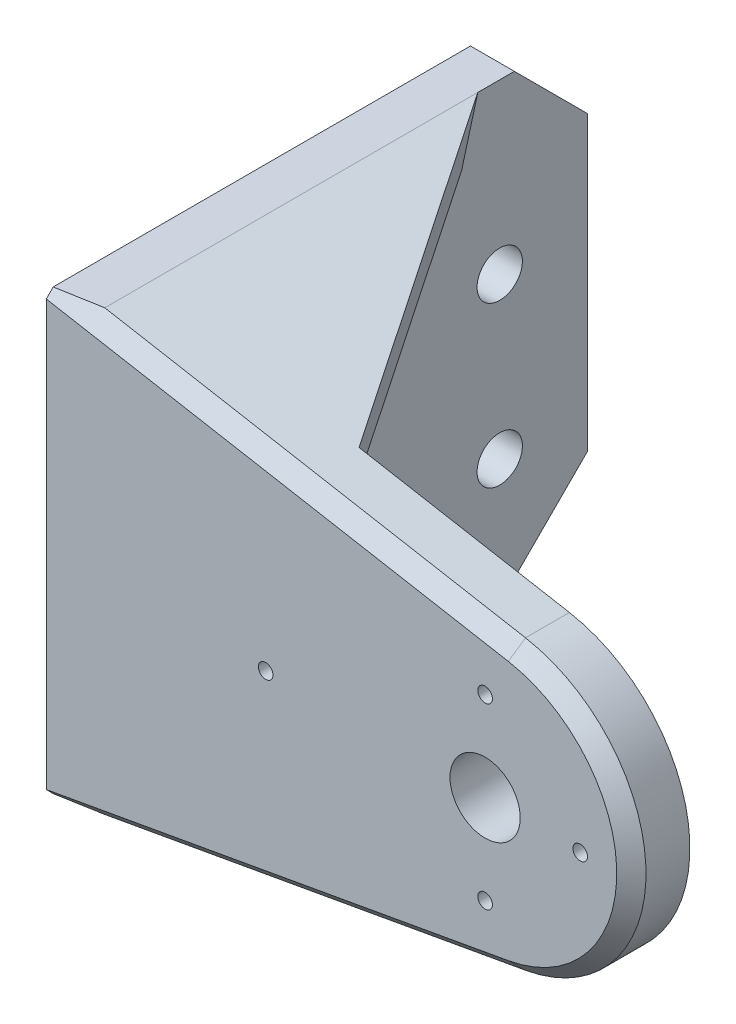
SolidWorks part; units mm, degrees
ref_plane "Front Plane" through (0, 0, 0) normal (0, 0, 1) x (1, 0, 0)
ref_plane "Top Plane" through (0, 0, 0) normal (0, 1, 0) x (1, 0, 0)
ref_plane "Right Plane" through (0, 0, 0) normal (1, 0, 0) x (0, 0, -1)
sketch "Sketch1" plane through (0, 0, 0) normal (0, 0, 1) x (1, 0, 0)
  line L0 (-24.444, 5.5562) -> (-24.444, -9.4438)
  line L1 (5.556, 5.5562) -> (-24.444, 5.5562) construction
  line L2 (-24.444, 5.5562) -> (-24.444, 20.5562)
  line L3 (-24.444, -9.4438) -> (-21.444, -9.4438)
  line L4 (-21.444, -9.4438) -> (7.3207, -4.2868)
  line L5 (-24.444, 20.5562) -> (-21.444, 20.5562)
  line L6 (-21.444, 20.5562) -> (7.3207, 15.3993)
  circle A1 centre (5.556, 5.5562) radius 1.984
  circle A2 centre (5.556, 5.5562) radius 10
  dimension "D1" = 20
  dimension "D2" = 30
  dimension "D3" = 15
  dimension "D4" = 15
  dimension "D5" = 3
  dimension "D6" = 3
extrude "Boss-Extrude1" add sketch "Sketch1" along normal blind 4 contours A2 L1 L0 L3 L4 | L1 A2 L6 L5 L2 | A1 A2 | A1 region at (-13.4785, -1.5234, 0) region at (-13.4785, 12.6359, 0) region at (5.556, 7.4841, 0) region at (-0.6794, 13.009, 0)
sketch "Sketch2" plane through (0, 0, 4) normal (0, 0, 1) x (1, 0, 0)
  circle A0 centre (5.556, 5.5562) radius 1.984 construction
  circle A1 centre (5.556, 5.5562) radius 1.984
  circle A2 centre (5.556, 5.5562) radius 1.05
  dimension "D1" = 2.1
sketch "Sketch3" plane through (0, 0, 0) normal (0, 0, -1) x (-1, 0, 0)
  line L0 (21.444, 20.5562) -> (21.444, -9.4438)
  line L1 (21.444, -9.4438) -> (24.444, -9.4438)
  line L2 (24.444, -9.4438) -> (24.444, 20.5562)
  line L3 (24.444, 20.5562) -> (21.444, 20.5562)
extrude "Boss-Extrude2" add sketch "Sketch3" along normal blind 30
sketch "Sketch4" plane through (2.9028, 16.1914, 0) normal (0.1765, 0.9843, 0) x (0.9843, -0.1765, 0)
  line L0 (-24.735, 22.5) -> (-10.1233, 0)
  line L1 (-24.735, 0) -> (4.4883, 0) construction
  line L3 (-24.735, 15) -> (-24.735, 30) construction
  line L4 (-24.735, 30) -> (-24.735, 0) construction
  line L5 (-10.1233, 0) -> (-10.1233, -0.5)
  line L6 (-10.1233, -0.5) -> (-24.735, -0.5)
  line L7 (-24.735, -4) -> (-24.735, 0) construction
  line L8 (-24.735, -0.5) -> (-24.735, 22.5)
  dimension "D1" = 0.5
extrude "Boss-Extrude3" add sketch "Sketch4" against normal blind 4
ref_axis "Axis1" through (5.556, 5.5562, 0) along (-1, 0, 0)
ref_plane "Plane1" through (0, 5.5562, 0) normal (0, 1, 0) x (-1, 0, 0)
chamfer "Chamfer1" distance 5 angle 45 1 edges at (-21.444, 3.5244, 0)
chamfer "Chamfer2" distance 5 angle 45 2 edges at (-22.944, -9.4438, -30) (-22.944, 20.5562, -30)
chamfer "Chamfer3" distance 1 angle 45 3 edges at (-7.0617, -6.8653, 4) (15.556, 5.5562, 4) (-7.0617, 17.9778, 4)
sketch "Sketch6" plane through (-21.444, 0, 0) normal (1, 0, 0) x (0, 0, -1)
  line L0 (30, 9.0472) -> (9.61, 9.0472) construction
  line L1 (30, 15.5562) -> (30, -4.4438) construction
  line L2 (30, -1.8898) -> (9.5502, -1.8898) construction
  line L3 (24, 9.0472) -> (24, -1.8898) construction
  line L4 (11, 9.0472) -> (11, -1.8898) construction
  circle A0 centre (11, 9.0472) radius 1.55
  circle A1 centre (24, 9.0472) radius 1.55
  circle A2 centre (11, -1.8898) radius 1.55
  circle A3 centre (24, -1.8898) radius 1.55
  dimension "D1" = 3.1
  dimension "D2" = 3.1
  dimension "D3" = 3.1
  dimension "D4" = 3.1
  dimension "D5" = 6
  dimension "D6" = 13
extrude "Cut-Extrude3" cut sketch "Sketch6" against normal up to next
sketch "Sketch7" plane through (0, 0, 0) normal (0, 0, -1) x (-1, 0, 0)
  circle A0 centre (-5.556, 5.5562) radius 1.05 construction
  circle A1 centre (-5.556, 5.5562) radius 1.05
  circle A2 centre (-5.556, 5.5562) radius 2.4
  dimension "D1" = 4.8
ref_point "Point1"
extrude "Cut-Extrude4" cut sketch "Sketch7" against normal up to next contours A2
sketch "Sketch8" plane through (0, 0, 0) normal (0, 0, -1) x (-1, 0, 0)
  circle A0 centre (9.444, 5.5563) radius 0.5 construction
  circle A1 centre (-5.556, 11.6562) radius 0.5 construction
  circle A2 centre (-5.556, -0.5438) radius 0.5 construction
  circle A3 centre (-12.056, 5.5562) radius 0.5 construction
  circle A4 centre (9.444, 5.5563) radius 0.5
  circle A5 centre (-5.556, 11.6562) radius 0.5
  circle A6 centre (-5.556, -0.5438) radius 0.5
  circle A7 centre (-12.056, 5.5562) radius 0.5
extrude "Cut-Extrude5" cut sketch "Sketch8" against normal up to next
